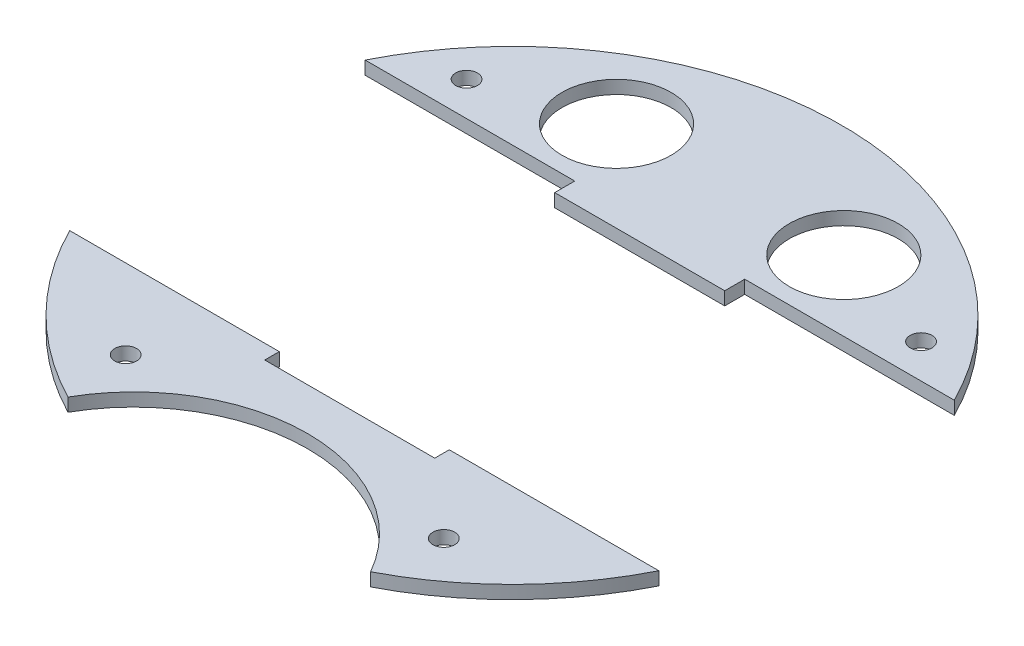
SolidWorks part; units mm, degrees
material "Acrylic (Medium-high impact)"
ref_plane "Front Plane" through (0, 0, 0) normal (0, 0, 1) x (1, 0, 0)
ref_plane "Top Plane" through (0, 0, 0) normal (0, 1, 0) x (1, 0, 0)
ref_plane "Right Plane" through (0, 0, 0) normal (1, 0, 0) x (0, 0, -1)
sketch "Sketch1" plane through (0, 0, 0) normal (0, 1, 0) x (1, 0, 0)
  line L0 (0, -83.2398) -> (-33.2911, -64.4046) construction
  line L1 (0, -83.2398) -> (0, 0) construction
  arc A0 (33.2911, -64.4046) -> (-33.2911, -64.4046) centre (0, 0) ccw
  arc A1 (33.2911, -64.4046) -> (-33.2911, -64.4046) centre (0, -83.2398) ccw
  dimension "D1" = 145
  dimension "D2" = 76.5
  dimension "D3" = 60.5
extrude "Boss-Extrude1" add sketch "Sketch1" along normal blind 2.9
sketch "solenoid placement" plane through (0, 2.9, 0) normal (0, 1, 0) x (1, 0, 0)
  line L4 (-18.7, -35.7) -> (18.7, -35.7)
  line L5 (18.7, -35.7) -> (18.7, 28.1)
  line L6 (18.7, 28.1) -> (-18.7, 28.1)
  line L7 (-18.7, 28.1) -> (-18.7, -35.7)
  line L8 (-18.7, -35.7) -> (18.7, -35.7)
  line L9 (18.7, -35.7) -> (18.7, 28.1)
  line L10 (18.7, 28.1) -> (-18.7, 28.1)
  line L11 (-18.7, 28.1) -> (-18.7, -35.7)
  circle A1 centre (0, 0) radius 72.5 construction
  arc A2 (33.2911, -64.4046) -> (-33.2911, -64.4046) centre (0, 0) ccw construction
  dimension "D1" = 0
extrude "Cut-Extrude1" cut sketch "solenoid placement" against normal through all
sketch "Sketch3" plane through (0, 2.9, 0) normal (0, 1, 0) x (1, 0, 0)
  circle A1 centre (25, 48) radius 12
  circle A2 centre (-25, 48) radius 12
  dimension "D1" = 24
extrude "Cut-Extrude3" cut sketch "Sketch3" against normal through all
sketch "Sketch4" plane through (0, 5.8, 0) normal (0, 1, 0) x (1, 0, 0)
  circle A1 centre (35, -50) radius 2.4
  circle A2 centre (35, -50) radius 2.4
  circle A3 centre (-35, -50) radius 2.4
  circle A4 centre (-35, -50) radius 2.4
  circle A5 centre (-50, 40) radius 2.4
  circle A6 centre (-50, 40) radius 2.4
  circle A7 centre (50, 40) radius 2.4
  circle A8 centre (50, 40) radius 2.4
  dimension "D1" = 0
  dimension "D2" = 0
  dimension "D3" = 0
  dimension "D4" = 0
extrude "Cut-Extrude4" cut sketch "Sketch4" against normal through all
sketch "Sketch2" plane through (0, 2.9, 0) normal (0, 1, 0) x (1, 0, 0)
  line L0 (-18.7, 28.1) -> (-18.7, 32.5)
  line L1 (-72.5, -32.5) -> (72.5, -32.5)
  line L2 (-72.5, -32.5) -> (-72.5, 32.5)
  line L3 (-72.5, 32.5) -> (-18.7, 32.5)
  line L4 (72.5, -32.5) -> (72.5, 32.5)
  line L5 (-72.5, -32.5) -> (72.5, 32.5) construction
  line L6 (-72.5, 32.5) -> (72.5, -32.5) construction
  line L7 (18.7, 28.1) -> (18.7, 32.5)
  line L8 (18.7, 28.1) -> (-18.7, 28.1)
  line L9 (18.7, 32.5) -> (72.5, 32.5)
  arc A0 (33.2911, -64.4046) -> (-33.2911, -64.4046) centre (0, 0) ccw construction
  point P0 (0, 0)
  dimension "D1" = 65
extrude "Cut-Extrude2" cut sketch "Sketch2" against normal through all
equation "\"smallPulleyTeeth\"= 15"
equation "\"largePulleyTeeth\"= 30"
equation "\"eighthThick\"= 2.9mm"
equation "\"sixteenthThick\" = 1.7mm"
equation "\"quarterThick\"=6.0mm"
equation "\"OD\" = 145mm"
equation "\"puckAngle\" = 60.5deg"
equation "\"D1@Sketch1\"=\"OD\""
equation "\"puckDiam\" = 76.5mm"
equation "\"D2@Sketch1\"=\"puckDiam\""
equation "\"D3@Sketch1\"=\"puckAngle\""
equation "\"D1@Boss-Extrude1\"=\"eighthThick\""
equation "\"axlePress\" = 5.9mm"
equation "\"press\" = 0.2mm"
equation "\"wheelClear\" = 0.3mm"
equation "\"10-32clear\" = 4.8mm"
equation "\"6-32clear\" = 3.3mm"
equation "\"8-32clear\" = 4.0mm"
equation "\"wheelHeight\" = 22mm"
equation "\"wheelWell\" = 65mm"
equation "\"D1@Sketch2\"=\"wheelWell\""
